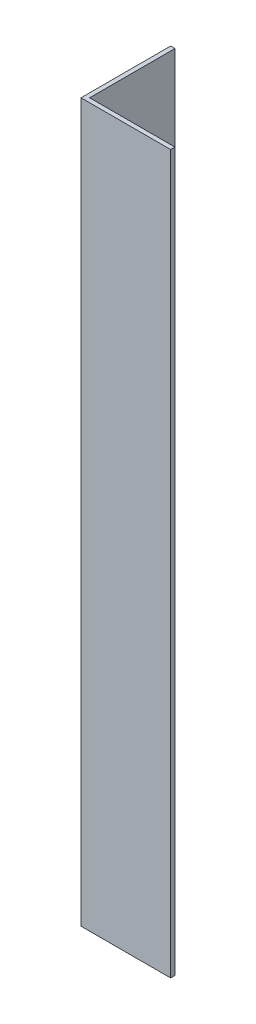
SolidWorks part; units mm, degrees
ref_plane "Front Plane" through (0, 0, 0) normal (0, 0, 1) x (1, 0, 0)
ref_plane "Top Plane" through (0, 0, 0) normal (0, 1, 0) x (1, 0, 0)
ref_plane "Right Plane" through (0, 0, 0) normal (1, 0, 0) x (0, 0, -1)
sketch "Sketch1" plane through (0, 0, 0) normal (0, 1, 0) x (1, 0, 0)
  line L1 (0, 0) -> (6.35, 0)
  line L2 (0, 0) -> (0, 6.35)
  line L3 (0, 6.35) -> (0.3048, 6.35)
  line L4 (6.35, 0) -> (6.35, 0.3048)
  line L7 (6.35, 0.3048) -> (0.3048, 0.3048)
  line L8 (0.3048, 6.35) -> (0.3048, 0.3048)
  dimension "D1" = 6.35
  dimension "D2" = 6.35
  dimension "D3" = 0.3048
  dimension "D4" = 0.3048
extrude "Boss-Extrude1" add sketch "Sketch1" along normal blind 50.8
